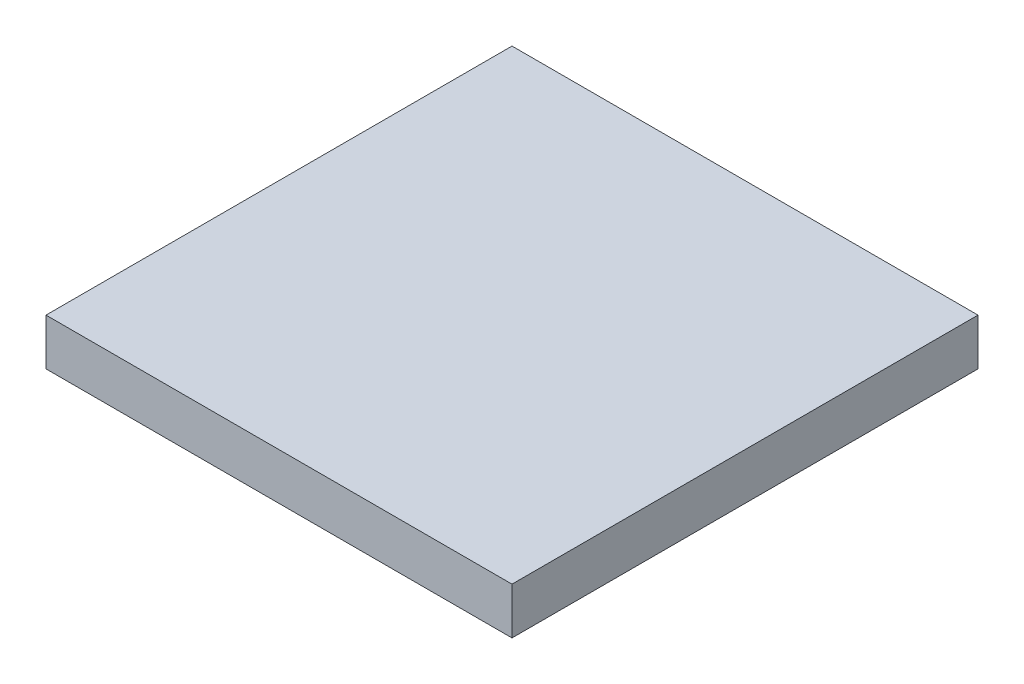
SolidWorks part; units mm, degrees
material "Pine"
ref_plane "Front Plane" through (0, 0, 0) normal (0, 0, 1) x (1, 0, 0)
ref_plane "Top Plane" through (0, 0, 0) normal (0, 1, 0) x (1, 0, 0)
ref_plane "Right Plane" through (0, 0, 0) normal (1, 0, 0) x (0, 0, -1)
sketch "Sketch1" plane through (0, 0, 0) normal (0, 1, 0) x (1, 0, 0)
  line L0 (0, -150) -> (0, 150) construction
  line L2 (-250, -150) -> (50, -150)
  line L3 (-250, -150) -> (-250, 150)
  line L4 (-250, 150) -> (50, 150)
  line L5 (50, -150) -> (50, 150)
  dimension "D1" = 50
  dimension "D2" = 300
  dimension "D3" = 300
extrude "Boss-Extrude1" add sketch "Sketch1" along normal blind 30
